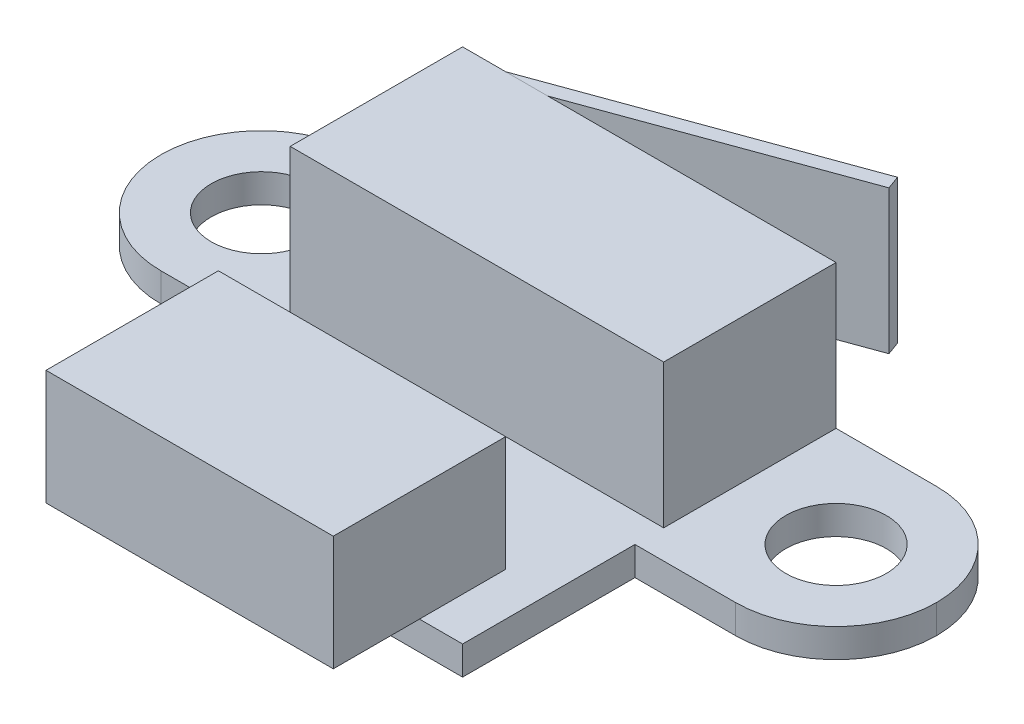
SolidWorks part; units mm, degrees
ref_plane "Front Plane" through (0, 0, 0) normal (0, 0, 1) x (1, 0, 0)
ref_plane "Top Plane" through (0, 0, 0) normal (0, 1, 0) x (1, 0, 0)
ref_plane "Right Plane" through (0, 0, 0) normal (1, 0, 0) x (0, 0, -1)
sketch "Sketch1" plane through (0, 0, 0) normal (0, 1, 0) x (1, 0, 0)
  line L1 (-6.5, -6.5) -> (6.5, -6.5)
  line L2 (-6.5, -6.5) -> (-6.5, 6.5)
  line L3 (-6.5, 6.5) -> (6.5, 6.5)
  line L4 (6.5, -6.5) -> (6.5, 6.5)
  line L5 (-6.5, -6.5) -> (6.5, 6.5) construction
  line L6 (-6.5, 6.5) -> (6.5, -6.5) construction
  point P0 (0, 0)
  dimension "D1" = 13
  dimension "D2" = 13
extrude "Boss-Extrude1" add sketch "Sketch1" along normal blind 1
sketch "Sketch4" plane through (-6.5, 0, 0) normal (-1, 0, 0) x (0, 0, 1)
  line L0 (-6.5, 1) -> (6.5, 1) construction
  line L1 (-6.5, 0) -> (0.5, 0)
  line L2 (-6.5, 0) -> (-6.5, 1)
  line L3 (-6.5, 1) -> (0.5, 1)
  line L4 (0.5, 0) -> (0.5, 1)
  dimension "D1" = 7
extrude "Boss-Extrude2" add sketch "Sketch4" along normal blind 7
sketch "Sketch5" plane through (6.5, 0, 0) normal (1, 0, 0) x (0, 0, -1)
  line L0 (-6.5, 0) -> (6.5, 0) construction
  line L1 (6.5, 1) -> (-0.5, 1)
  line L2 (6.5, 1) -> (6.5, 0)
  line L3 (6.5, 0) -> (-0.5, 0)
  line L4 (-0.5, 1) -> (-0.5, 0)
  dimension "D1" = 7
extrude "Boss-Extrude3" add sketch "Sketch5" along normal blind 7
sketch "Sketch6" plane through (0, 1, 0) normal (0, 1, 0) x (1, 0, 0)
  line L0 (-13.5, -0.5) -> (-6.5, -0.5) construction
  line L2 (-13.5, -0.5) -> (-13.5, 6.5) construction
  circle A0 centre (-10, 3) radius 1.75
  circle A1 centre (10, 3) radius 1.75
  dimension "D1" = 3.5
  dimension "D4" = 3.5
  dimension "D2" = 3.5
  dimension "D3" = 3.5
  dimension "D5" = 20
extrude "Cut-Extrude1" cut sketch "Sketch6" against normal through all
sketch "Sketch7" plane through (0, 1, 0) normal (0, 1, 0) x (1, 0, 0)
  line L0 (13.5, 6.5) -> (-13.5, 6.5) construction
  line L1 (-5, -3.5) -> (5, -3.5)
  line L2 (-5, -3.5) -> (-5, -9.5)
  line L3 (-5, -9.5) -> (5, -9.5)
  line L4 (5, -3.5) -> (5, -9.5)
  line L5 (-6.5, -0.5) -> (-6.5, -6.5) construction
  dimension "D1" = 6
  dimension "D2" = 10
  dimension "D3" = 10
  dimension "D4" = 1.5
extrude "Boss-Extrude4" add sketch "Sketch7" along normal blind 4
sketch "Sketch8" plane through (0, 1, 0) normal (0, 1, 0) x (1, 0, 0)
  line L0 (-6.5, -0.5) -> (-6.5, -6.5) construction
  line L1 (-6.5, 0.5) -> (6.5, 0.5)
  line L2 (-6.5, 0.5) -> (-6.5, 6.5)
  line L3 (-6.5, 6.5) -> (6.5, 6.5)
  line L4 (6.5, 0.5) -> (6.5, 6.5)
  line L5 (13.5, 6.5) -> (-13.5, 6.5) construction
  dimension "D1" = 13
  dimension "D2" = 0
  dimension "D3" = 6
  dimension "D4" = 0
extrude "Boss-Extrude5" add sketch "Sketch8" along normal blind 5
sketch "Sketch12" plane through (0, 6, 0) normal (0, 1, 0) x (1, 0, 0)
  line L0 (-5, 6.5) -> (5, 10.1397)
  line L1 (6.5, 6.5) -> (-6.5, 6.5) construction
  line L2 (5, 10.1397) -> (5.171, 9.6699)
  line L3 (5.171, 9.6699) -> (-3.5381, 6.5)
  line L4 (-3.5381, 6.5) -> (-5, 6.5)
  dimension "D1" = 20
  dimension "D2" = 1.5
  dimension "D3" = 10
  dimension "D4" = 0.5
extrude "Boss-Extrude7" add sketch "Sketch12" against normal blind 5 separate body
fillet "Fillet1" radius 3.5 4 edges at (13.5, 0.5, -6.5) (13.5, 0.5, 0.5) (-13.5, 0.5, 0.5) (-13.5, 0.5, -6.5)
